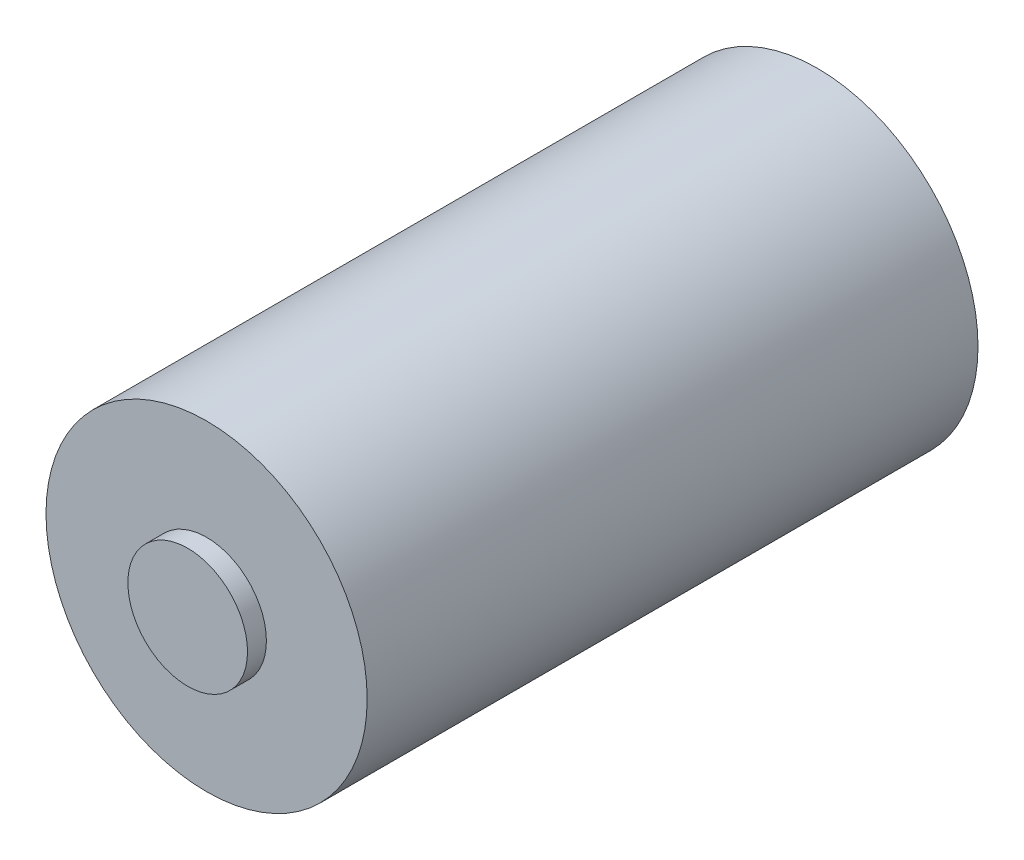
SolidWorks part; units mm, degrees
ref_plane "Plan de face" through (0, 0, 0) normal (0, 0, 1) x (1, 0, 0)
ref_plane "Plan de dessus" through (0, 0, 0) normal (0, 1, 0) x (1, 0, 0)
ref_plane "Plan de droite" through (0, 0, 0) normal (1, 0, 0) x (0, 0, -1)
sketch "Esquisse1" plane through (0, 0, 0) normal (0, 0, 1) x (1, 0, 0)
  circle A0 centre (0, 0) radius 12.75
  dimension "D1" = 25.5
extrude "Boss.-Extru.1" add sketch "Esquisse1" along normal blind 50
sketch "Esquisse2" plane through (0, 0, 50) normal (0, 0, 1) x (1, 0, 0)
  circle A0 centre (0, 0) radius 4.75
  circle A1 centre (0, 0) radius 12.75
  circle A2 centre (0, 0) radius 12.75 construction
  dimension "D1" = 9.5
extrude "Enlèv. mat.-Extru.1" cut sketch "Esquisse2" against normal blind 1.5
sketch3d "3DSketch3" plane through (0, 0, 0) normal (0, 0, 1) x (1, 0, 0)
sketch "Sketch2" plane through (2.4899, -12.5045, 0) normal (0.1953, -0.9807, 0) x (-0.9807, -0.1953, 0)
  line L0 (1.2994, -54.6514) -> (-30.3966, -54.6514) construction
  line L5 (1.2994, -2.3593) -> (-13.3732, -2.3593) construction
  text T0 "+" font "Century Gothic" height in points 18
  text T1 "-" font "Century Gothic" height in points 18
wrap "Wrap1" sketch "Sketch2" wrap type scribe source sketch "Sketch2" face at (12.75, 0, 0)
